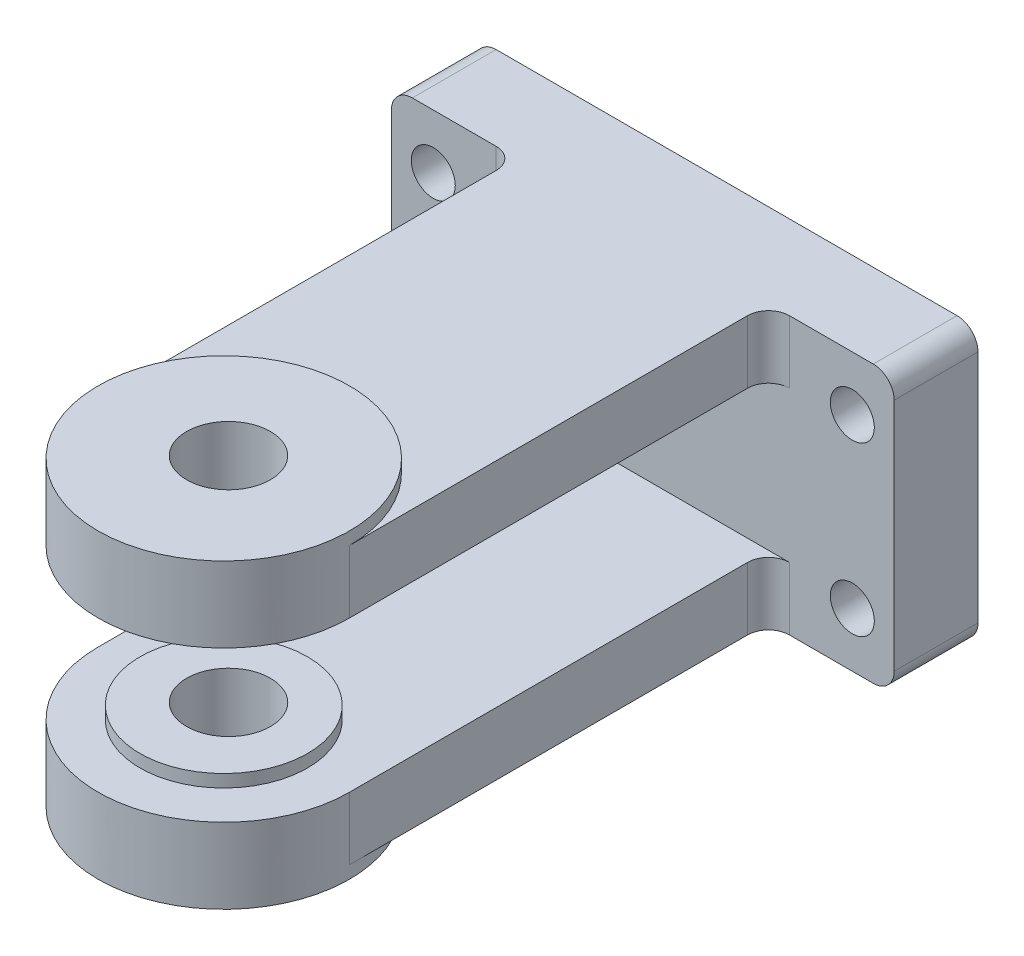
SolidWorks part; units mm, degrees
ref_plane "Ön Düzlem" through (0, 0, 0) normal (0, 0, 1) x (1, 0, 0)
ref_plane "Üst Düzlem" through (0, 0, 0) normal (0, 1, 0) x (1, 0, 0)
ref_plane "Sağ Düzlem" through (0, 0, 0) normal (1, 0, 0) x (0, 0, -1)
sketch "Çizim1" plane through (0, 0, 0) normal (0, 0, 1) x (1, 0, 0)
  line L1 (-55, 33) -> (55, 33)
  line L2 (-60, 28) -> (-60, -28)
  line L3 (-55, -33) -> (55, -33)
  line L4 (60, 28) -> (60, -28)
  line L5 (-60, 33) -> (60, -33) construction
  line L6 (-60, -33) -> (60, 33) construction
  arc A0 (55, 33) -> (60, 28) centre (55, 28) cw
  arc A1 (-60, -28) -> (-55, -33) centre (-55, -28) ccw
  arc A2 (-55, 33) -> (-60, 28) centre (-55, 28) ccw
  arc A3 (55, -33) -> (60, -28) centre (55, -28) ccw
  point P0 (0, 0)
  dimension "D3" = 5
  dimension "D1" = 120
  dimension "D2" = 66
extrude "Yükseklik-Ekstrüzyon1" add sketch "Çizim1" along normal blind 20
sketch "Çizim2" plane through (0, 33, 0) normal (0, 1, 0) x (1, 0, 0)
  line L0 (55, -20) -> (-55, -20) construction
  line L1 (-30, -20) -> (30, -20)
  line L2 (-30, -20) -> (-30, -120)
  line L4 (30, -20) -> (30, -120)
  arc A0 (-30, -120) -> (30, -120) centre (0, -120) ccw
  point P6 (0, -20)
  dimension "D1" = 100
  dimension "D2" = 30
extrude "Yükseklik-Ekstrüzyon2" add sketch "Çizim2" against normal blind 15
sketch "Çizim3" plane through (0, 33, 0) normal (0, 1, 0) x (1, 0, 0)
  circle A0 centre (0, -120) radius 30
extrude "Yükseklik-Ekstrüzyon3" add sketch "Çizim3" along normal blind 3
sketch "Çizim4" plane through (0, 18, 0) normal (0, -1, 0) x (-1, 0, 0)
  circle A0 centre (0, -120) radius 20
  dimension "D1" = 40
extrude "Yükseklik-Ekstrüzyon4" add sketch "Çizim4" along normal blind 3
sketch "Çizim5" plane through (0, 15, 0) normal (0, -1, 0) x (1, 0, 0)
  circle A0 centre (0, 118.8679) radius 10
  dimension "D1" = 20
extrude "Kes-Ekstrüzyon1" cut sketch "Çizim5" against normal through all
ref_plane "Düzlem1" through (0, 0, 0) normal (0, -1, 0) x (-1, 0, 0)
mirror "Aynalama1" about plane through (0, 0, 0) normal (0, -1, 0) of "Kes-Ekstrüzyon1", "Yükseklik-Ekstrüzyon4", "Yükseklik-Ekstrüzyon3", "Yükseklik-Ekstrüzyon2", "Yükseklik-Ekstrüzyon1"
sketch "Çizim6" plane through (0, 0, 20) normal (0, 0, 1) x (1, 0, 0)
  line L0 (-60, 28) -> (-60, -28) construction
  line L1 (-55, -33) -> (-30, -33) construction
  line L3 (0, -11.7906) -> (0, 11.4421) construction
  circle A0 centre (-50, 20) radius 5.25
  circle A1 centre (-50, -20) radius 5.25
  circle A2 centre (50, -20) radius 5.25
  circle A3 centre (50, 20) radius 5.25
  dimension "D5" = 10.5
  dimension "D6" = 10.5
  dimension "D1" = 40
  dimension "D2" = 10
  dimension "D3" = 10
  dimension "D4" = 13
extrude "Kes-Ekstrüzyon2" cut sketch "Çizim6" against normal through all
fillet "Radyus1" radius 5 4 edges at (-30, -25.5, 20) (-30, 25.5, 20) (30, -25.5, 20) (30, 25.5, 20)
